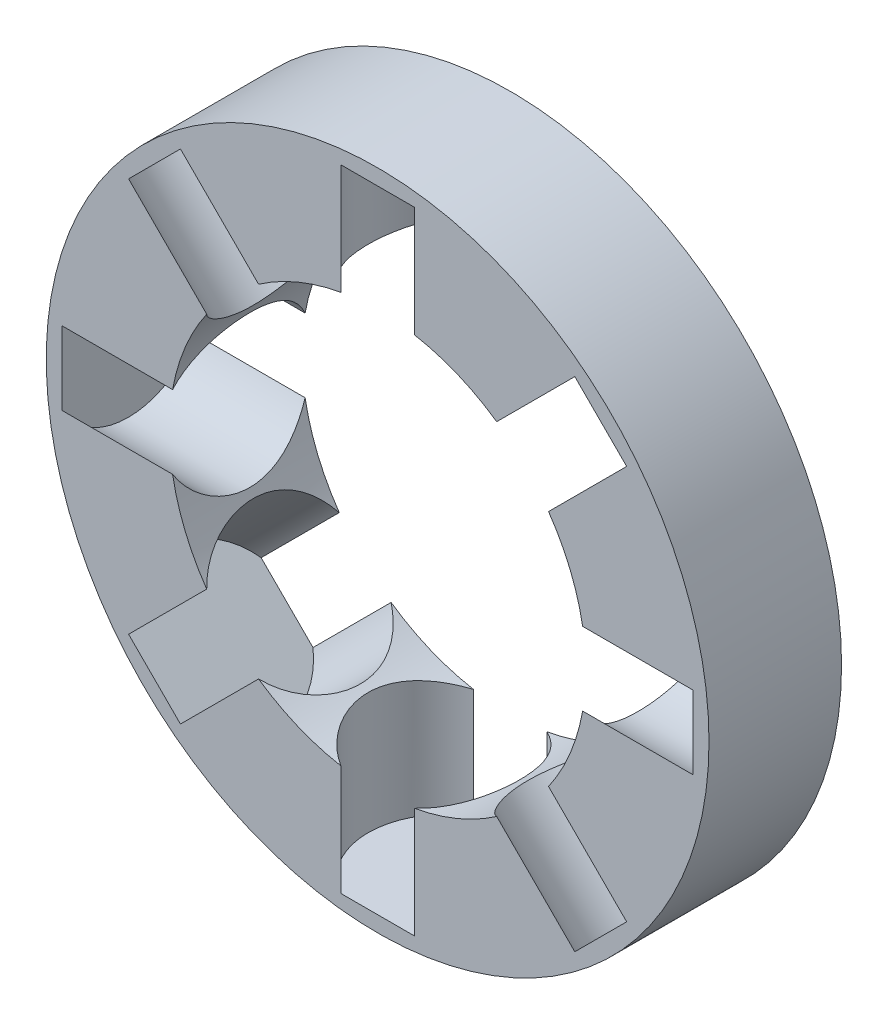
SolidWorks part; units mm, degrees
ref_plane "Top Plane" through (0, 0, 0) normal (0, 0, 1) x (1, 0, 0)
ref_plane "Right Plane" through (0, 0, 0) normal (0, 1, 0) x (1, 0, 0)
ref_plane "Front Plane" through (0, 0, 0) normal (1, 0, 0) x (0, 0, -1)
ref_axis "x-axis" through (-88.99, 0, 0) along (1, 0, 0)
ref_axis "y-axis" through (0, -55, 0) along (0, 1, 0)
ref_axis "z-axis" through (0, 0, 55) along (0, 0, -1)
sketch "Sketch1" plane through (0, 0, 0) normal (0, 0, 1) x (1, 0, 0)
  circle A0 centre (0, 0) radius 11
  circle A1 centre (0, 0) radius 17.5
  dimension "D1" = 22
  dimension "D2" = 6.5
extrude "Boss-Extrude1" add sketch "Sketch1" along normal mid plane 7
sketch "Sketch3" plane through (0, 0, 0) normal (0, 0, 1) x (1, 0, 0)
  line L0 (10.1627, -4.2095) -> (10.1627, 4.2095) construction
  line L1 (-10.1627, 4.2095) -> (-10.1627, -4.2095) construction
  line L2 (-10.1627, -4.2095) -> (-4.2095, -10.1627) construction
  line L3 (-4.2095, -10.1627) -> (4.2095, -10.1627) construction
  line L4 (4.2095, -10.1627) -> (10.1627, -4.2095) construction
  line L5 (10.1627, 4.2095) -> (4.2095, 10.1627) construction
  line L6 (4.2095, 10.1627) -> (-4.2095, 10.1627) construction
  line L7 (-4.2095, 10.1627) -> (-10.1627, 4.2095) construction
  line L8 (0, -55) -> (0, 55) construction
  circle A0 centre (0, 0) radius 10.1627 construction
  circle A2 centre (0, 0) radius 11 construction
  point P15 (0, 10.1627)
ref_plane "Plane1" through (-10.1627, 0, 0) normal (1, 0, 0) x (0, 0, -1)
sketch "Sketch4" plane through (-10.1627, 0, 0) normal (1, 0, 0) x (0, 0, -1)
  line L0 (0, 4.2095) -> (0, -4.2095) construction
  circle A0 centre (0, 0) radius 4
  dimension "D1" = 8
extrude "Cut-Extrude1" cut sketch "Sketch4" against normal blind 6.5
pattern_circular "CirPattern1" count 8 over 360 about axis through (0, 0, 3.5) along (0, 0, -1) of "Cut-Extrude1"
